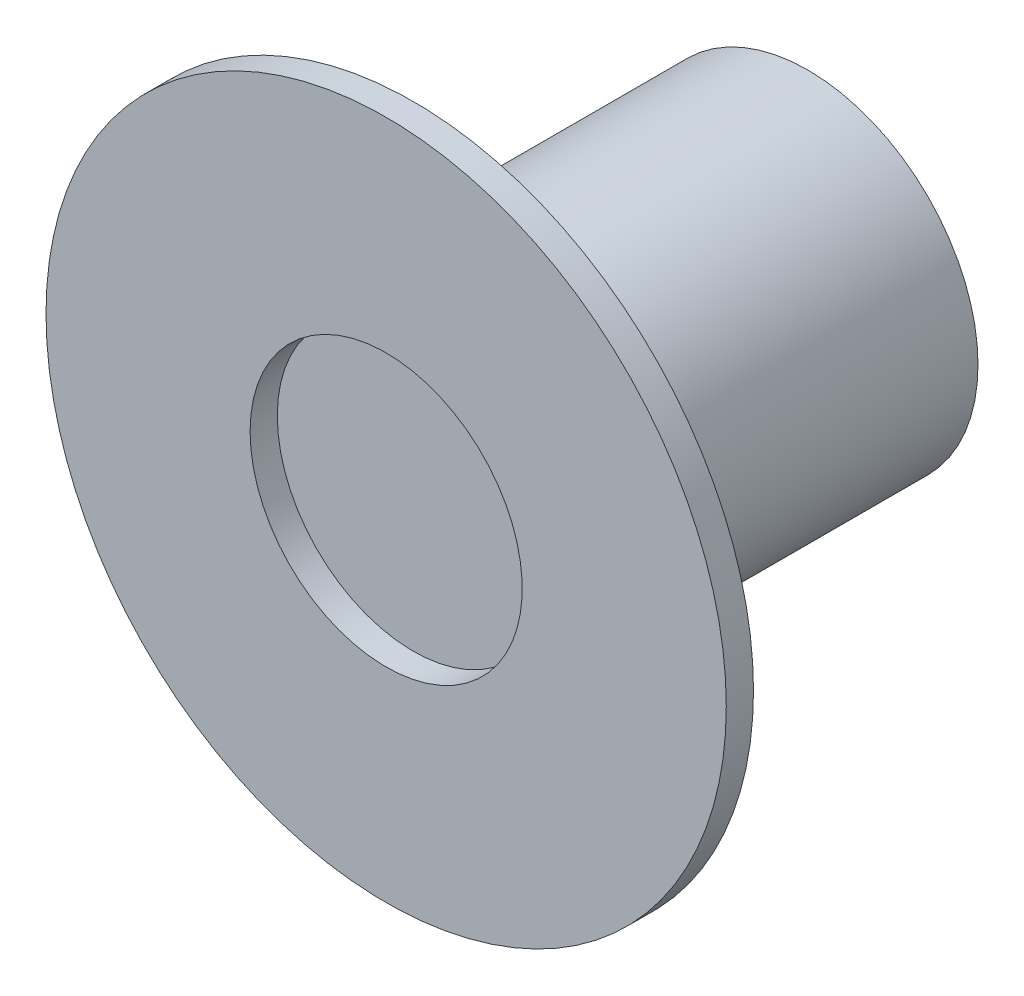
SolidWorks part; units mm, degrees
other "마크업1"
sketch "스케치14" plane through (30, 31, -30.5354) normal (0.2605, 0.9636, -0.0594) x (0.9655, -0.2601, 0.014)
sketch "스케치15" plane through (30, 31, -30.5354) normal (0.2605, 0.9636, -0.0594) x (0.9655, -0.2601, 0.014)
sketch "스케치16" plane through (30, 31, -30.5354) normal (0.2605, 0.9636, -0.0594) x (0.9655, -0.2601, 0.014)
sketch "스케치21" plane through (30, 31, -30.5354) normal (0.2605, 0.9636, -0.0594) x (0.9655, -0.2601, 0.014)
sketch "스케치23" plane through (30, 275, -27) normal (0.2605, 0.9636, -0.0594) x (0.9655, -0.2601, 0.014)
sketch "스케치28" plane through (20, 265, -24) normal (0.2605, 0.9636, -0.0594) x (0.9655, -0.2601, 0.014)
sketch "스케치31" plane through (20, 265, -24) normal (0.2605, 0.9636, -0.0594) x (0.9655, -0.2601, 0.014)
sketch "스케치32" plane through (20, 265, -23) normal (0.2605, 0.9636, -0.0594) x (0.9655, -0.2601, 0.014)
sketch "스케치33" plane through (20, 265, -23) normal (0.2605, 0.9636, -0.0594) x (0.9655, -0.2601, 0.014)
sketch "스케치38" plane through (25, 25, -31) normal (0.2605, 0.9636, -0.0594) x (0.9655, -0.2601, 0.014)
material "7075-T6, 플레이트 (SS)"
ref_plane "정면" through (0, 0, 0) normal (0, 0, 1) x (1, 0, 0)
ref_plane "윗면" through (0, 0, 0) normal (0, 1, 0) x (1, 0, 0)
ref_plane "우측면" through (0, 0, 0) normal (1, 0, 0) x (0, 0, -1)
sketch "스케치2" plane through (0, 6, 0) normal (0, 0, -1) x (1, 0, 0)
  circle A0 centre (0, 6) radius 10
  circle A1 centre (0, 6) radius 25
  dimension "D1" = 50
  dimension "30" = 20
extrude "보스-돌출2" add sketch "스케치2" along normal blind 2
sketch "스케치35" plane through (0, 0, -2) normal (0, 0, -1) x (-1, 0, 0)
  circle A0 centre (0, 0) radius 13.5
  dimension "D1" = 27
extrude "보스-돌출3" add sketch "스케치35" along normal blind 2
sketch "스케치36" plane through (0, 0, -4) normal (0, 0, -1) x (-1, 0, 0)
  circle A0 centre (0, 0) radius 12.5
  dimension "D1" = 25
extrude "보스-돌출4" add sketch "스케치36" along normal blind 27
sketch "스케치37" plane through (0, 0, -31) normal (0, 0, -1) x (-1, 0, 0)
  circle A0 centre (0, 0) radius 10
  dimension "D1" = 20
extrude "컷-돌출3" cut sketch "스케치37" against normal blind 3
